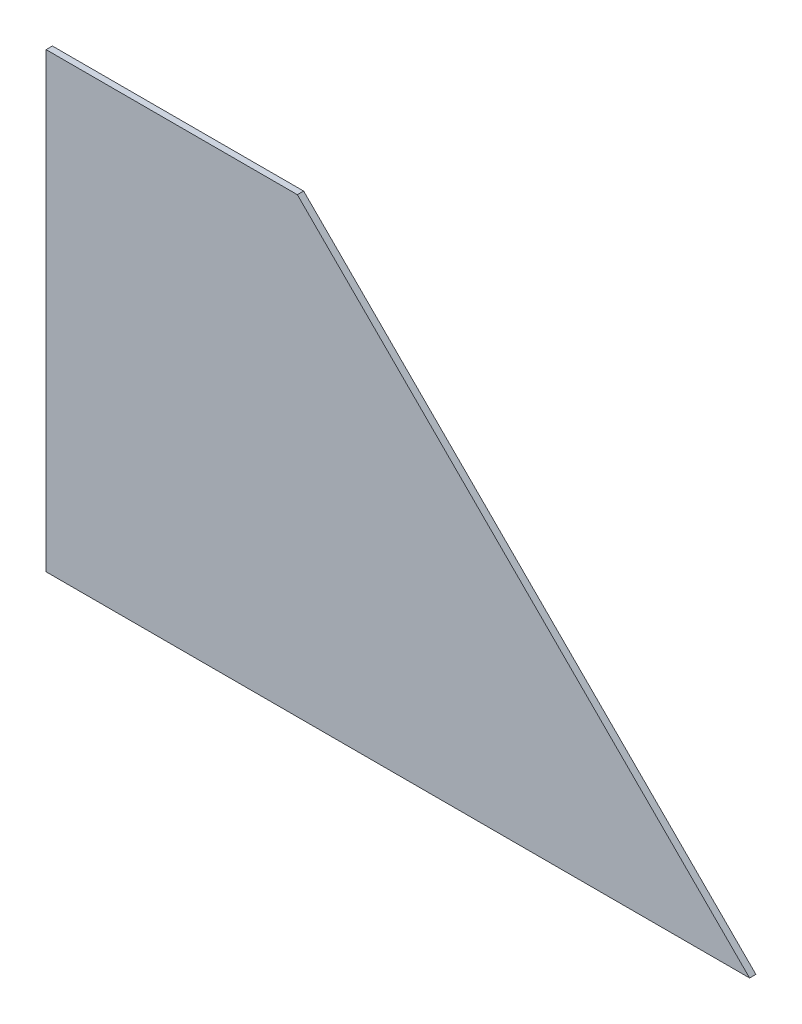
SolidWorks part; units mm, degrees
ref_plane "Front Plane" through (0, 0, 0) normal (0, 0, 1) x (1, 0, 0)
ref_plane "Top Plane" through (0, 0, 0) normal (0, 1, 0) x (1, 0, 0)
ref_plane "Right Plane" through (0, 0, 0) normal (1, 0, 0) x (0, 0, -1)
sketch "Sketch1" plane through (0, 0, 0) normal (0, 0, 1) x (1, 0, 0)
  line L0 (127, 228.6) -> (355.6, 0)
  line L1 (0, 0) -> (127, 0)
  line L2 (0, 0) -> (0, 228.6)
  line L3 (0, 228.6) -> (127, 228.6)
  line L5 (355.6, 0) -> (127, 0)
  dimension "D1" = 127
  dimension "D2" = 228.6
  dimension "D3" = 45
extrude "Boss-Extrude1" add sketch "Sketch1" along normal blind 3.175
